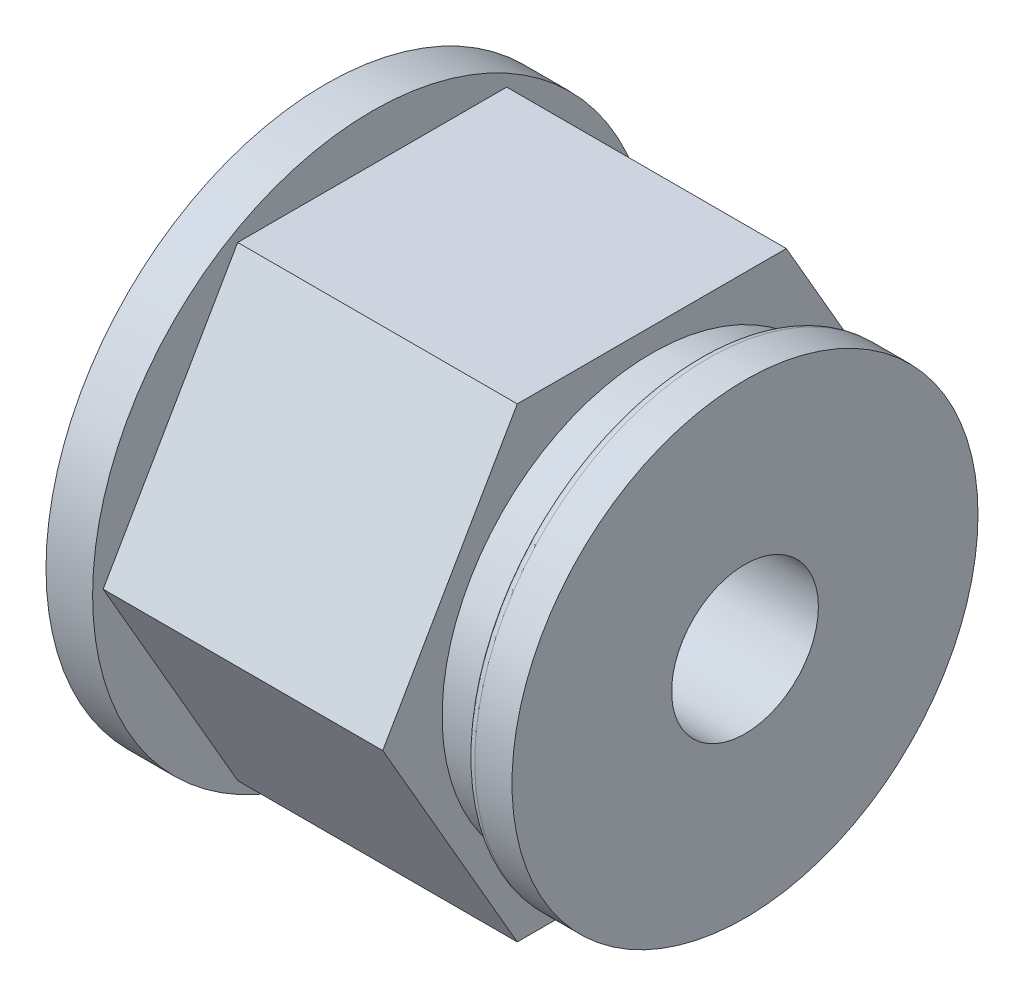
SolidWorks part; units mm, degrees
ref_plane "Front" through (0, 0, 0) normal (0, 0, 1) x (1, 0, 0)
ref_plane "Top" through (0, 0, 0) normal (0, 1, 0) x (1, 0, 0)
ref_plane "Right" through (0, 0, 0) normal (1, 0, 0) x (0, 0, -1)
sketch "Sketch2" plane through (0, 0, 0) normal (1, 0, 0) x (0, 0, -1)
  circle A0 centre (0, 0) radius 7.62
  dimension "D1" = 15.24
extrude "Boss-Extrude1" add sketch "Sketch2" against normal blind 1.27
sketch "Sketch3" plane through (0, 0, 0) normal (1, 0, 0) x (0, 0, -1)
  line L1 (-3.6662, 6.35) -> (-7.3323, 0)
  line L2 (-7.3323, 0) -> (-3.6662, -6.35)
  line L3 (-3.6662, -6.35) -> (3.6662, -6.35)
  line L4 (3.6662, -6.35) -> (7.3323, 0)
  line L5 (7.3323, 0) -> (3.6662, 6.35)
  line L6 (3.6662, 6.35) -> (-3.6662, 6.35)
  circle A0 centre (0, 0) radius 6.35 construction
  dimension "D1" = 12.7
extrude "Boss-Extrude2" add sketch "Sketch3" along normal blind 7.62
sketch "Sketch4" plane through (7.62, 0, 0) normal (1, 0, 0) x (0, 0, -1)
  circle A0 centre (0, 0) radius 5.715
  dimension "D1" = 11.43
extrude "Boss-Extrude3" add sketch "Sketch4" along normal blind 1.27
sketch "Sketch5" plane through (8.89, 0, 0) normal (1, 0, 0) x (0, 0, -1)
  circle A0 centre (0, 0) radius 6.35
  dimension "D1" = 12.7
extrude "Boss-Extrude4" add sketch "Sketch5" along normal blind 1.27
fillet "Fillet1" radius 0.254 2 edges at (8.89, 0, -6.35) (8.89, 0, -5.715)
sketch "Sketch6" plane through (10.16, 0, 0) normal (1, 0, 0) x (0, 0, -1)
  circle A0 centre (0, 0) radius 2
  dimension "D1" = 4
extrude "Cut-Extrude1" cut sketch "Sketch6" against normal up to surface (11.43 mm away) up to face at (-1.27, 0, -7.62)
